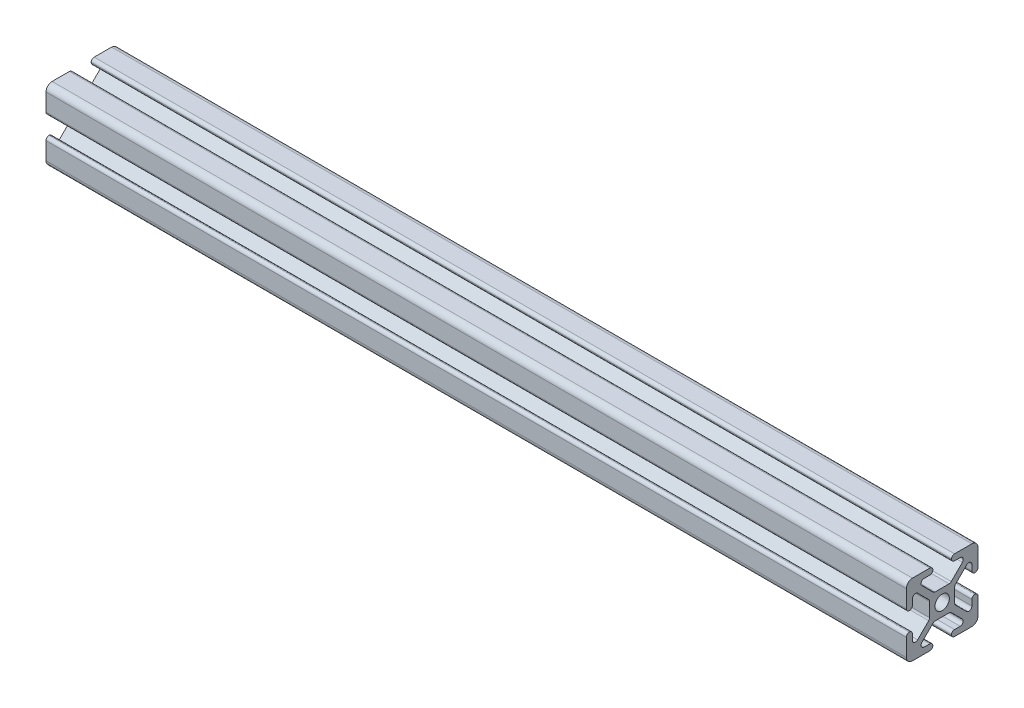
SolidWorks part; units mm, degrees
ref_plane "Front Plane" through (0, 0, 0) normal (1, 0, 0) x (0, 1, 0)
ref_plane "Top Plane" through (0, 0, 0) normal (0, 0, 1) x (0, 1, 0)
ref_plane "Right Plane" through (0, 0, 0) normal (0, 1, 0) x (-1, 0, 0)
sketch "Sketch1" plane through (0, 0, 0) normal (1, 0, 0) x (0, 1, 0)
  line L0 (0, 0) -> (0, 12.5) construction
  line L1 (-12.5, -12.5) -> (12.5, -12.5)
  line L2 (-12.5, -12.5) -> (-12.5, 12.5)
  line L3 (-12.5, 12.5) -> (12.5, 12.5)
  line L4 (12.5, -12.5) -> (12.5, 12.5)
  line L5 (-12.5, -12.5) -> (12.5, 12.5) construction
  line L6 (-12.5, 12.5) -> (12.5, -12.5) construction
  line L7 (-3.25, 12.5) -> (-3.25, 10.37)
  line L8 (-3.25, 10.37) -> (-8.8639, 10.37)
  line L9 (-8.8639, 10.37) -> (-2.8739, 4.38)
  line L10 (-2.8739, 4.38) -> (2.8739, 4.38)
  line L11 (8.8639, 10.37) -> (2.8739, 4.38)
  line L12 (3.25, 10.37) -> (8.8639, 10.37)
  line L13 (3.25, 12.5) -> (3.25, 10.37)
  line L14 (12.5, -3.25) -> (10.37, -3.25)
  line L15 (10.37, -3.25) -> (10.37, -8.8639)
  line L16 (10.37, -8.8639) -> (4.38, -2.8739)
  line L17 (4.38, 2.8739) -> (4.38, -2.8739)
  line L18 (10.37, 8.8639) -> (4.38, 2.8739)
  line L19 (10.37, 3.25) -> (10.37, 8.8639)
  line L20 (12.5, 3.25) -> (10.37, 3.25)
  line L21 (-3.25, -12.5) -> (-3.25, -10.37)
  line L22 (-3.25, -10.37) -> (-8.8639, -10.37)
  line L23 (-8.8639, -10.37) -> (-2.8739, -4.38)
  line L24 (2.8739, -4.38) -> (-2.8739, -4.38)
  line L25 (8.8639, -10.37) -> (2.8739, -4.38)
  line L26 (3.25, -10.37) -> (8.8639, -10.37)
  line L27 (3.25, -12.5) -> (3.25, -10.37)
  line L28 (-12.5, 3.25) -> (-10.37, 3.25)
  line L29 (-10.37, 3.25) -> (-10.37, 8.8639)
  line L30 (-10.37, 8.8639) -> (-4.38, 2.8739)
  line L31 (-4.38, -2.8739) -> (-4.38, 2.8739)
  line L32 (-10.37, -8.8639) -> (-4.38, -2.8739)
  line L33 (-10.37, -3.25) -> (-10.37, -8.8639)
  line L34 (-12.5, -3.25) -> (-10.37, -3.25)
  circle A0 centre (0, 0) radius 2.5
  point P0 (0, 0)
  point P15 (0, 4.38)
  dimension "D3" = 5
  dimension "D1" = 25
  dimension "D2" = 25
  dimension "D4" = 2.13
  dimension "D5" = 2.13
  dimension "D6" = 6.5
  dimension "D7" = 4.38
  dimension "D8" = 4
extrude "Boss-Extrude1" add sketch "Sketch1" along normal blind 300 contours L34 L2 L1 L21 L22 L23 L24 L25 L26 L27 L4 L14 L15 L16 L17 L18 L19 L20 L3 L13 L12 L11 L10 L9 L8 L7 L28 L29 L30 L31 L32 L33 A0 region at (0, -12.1464, -7.875)
fillet "Fillet1" radius 1.065 32 edges at (150, -10.37, -8.8639) (150, 2.8739, -4.38) (150, -2.8739, -4.38) (150, -4.38, 2.8739) (150, -4.38, -2.8739) (150, -2.8739, 4.38) (150, 2.8739, 4.38) (150, 4.38, 2.8739) (150, 4.38, -2.8739) (150, -8.8639, -10.37) (150, 8.8639, -10.37) (150, 10.37, -8.8639) (150, -10.37, 8.8639) (150, -8.8639, 10.37) (150, 10.37, 8.8639) (150, 8.8639, 10.37) (150, 12.5, 3.25) (150, -3.25, -12.5) (150, -10.37, 3.25) (150, 10.37, 3.25) (150, -10.37, -3.25) (150, -12.5, -3.25) (150, -12.5, 3.25) (150, 3.25, -10.37) (150, -3.25, -10.37) (150, 3.25, -12.5) (150, 10.37, -3.25) (150, 12.5, -3.25) (150, 3.25, 12.5) (150, 3.25, 10.37) (150, -3.25, 10.37) (150, -3.25, 12.5)
fillet "Fillet2" radius 2.13 4 edges at (150, 12.5, -12.5) (150, -12.5, -12.5) (150, 12.5, 12.5) (150, -12.5, 12.5)
sketch "Sketch2" plane through (300, 0, 0) normal (1, 0, 0) x (0, 1, 0)
  line L0 (10.37, -12.5) -> (4.315, -12.5)
  line L1 (10.37, -12.5) -> (4.315, -12.5)
  line L2 (4.315, -10.37) -> (6.2927, -10.37)
  line L3 (4.315, -10.37) -> (6.2927, -10.37)
  line L4 (7.0458, -8.5519) -> (3.1858, -4.6919)
  line L5 (7.0458, -8.5519) -> (3.1858, -4.6919)
  line L6 (2.4327, -4.38) -> (-2.4327, -4.38)
  line L7 (2.4327, -4.38) -> (-2.4327, -4.38)
  line L8 (-3.1858, -4.6919) -> (-7.0458, -8.5519)
  line L9 (-3.1858, -4.6919) -> (-7.0458, -8.5519)
  line L10 (-6.2927, -10.37) -> (-4.315, -10.37)
  line L11 (-6.2927, -10.37) -> (-4.315, -10.37)
  line L12 (-4.315, -12.5) -> (-10.37, -12.5)
  line L13 (-4.315, -12.5) -> (-10.37, -12.5)
  line L14 (-12.5, -10.37) -> (-12.5, -4.315)
  line L15 (-12.5, -10.37) -> (-12.5, -4.315)
  line L16 (-10.37, -4.315) -> (-10.37, -6.2927)
  line L17 (-10.37, -4.315) -> (-10.37, -6.2927)
  line L18 (-8.5519, -7.0458) -> (-4.6919, -3.1858)
  line L19 (-8.5519, -7.0458) -> (-4.6919, -3.1858)
  line L20 (-4.38, -2.4327) -> (-4.38, 2.4327)
  line L21 (-4.38, -2.4327) -> (-4.38, 2.4327)
  line L22 (-4.6919, 3.1858) -> (-8.5519, 7.0458)
  line L23 (-4.6919, 3.1858) -> (-8.5519, 7.0458)
  line L24 (-10.37, 6.2927) -> (-10.37, 4.315)
  line L25 (-10.37, 6.2927) -> (-10.37, 4.315)
  line L26 (-12.5, 4.315) -> (-12.5, 10.37)
  line L27 (-12.5, 4.315) -> (-12.5, 10.37)
  line L28 (-10.37, 12.5) -> (-4.315, 12.5)
  line L29 (-10.37, 12.5) -> (-4.315, 12.5)
  line L30 (-4.315, 10.37) -> (-6.2927, 10.37)
  line L31 (-4.315, 10.37) -> (-6.2927, 10.37)
  line L32 (-7.0458, 8.5519) -> (-3.1858, 4.6919)
  line L33 (-7.0458, 8.5519) -> (-3.1858, 4.6919)
  line L34 (-2.4327, 4.38) -> (2.4327, 4.38)
  line L35 (-2.4327, 4.38) -> (2.4327, 4.38)
  line L36 (3.1858, 4.6919) -> (7.0458, 8.5519)
  line L37 (3.1858, 4.6919) -> (7.0458, 8.5519)
  line L38 (6.2927, 10.37) -> (4.315, 10.37)
  line L39 (6.2927, 10.37) -> (4.315, 10.37)
  line L40 (4.315, 12.5) -> (10.37, 12.5)
  line L41 (4.315, 12.5) -> (10.37, 12.5)
  line L42 (12.5, 10.37) -> (12.5, 4.315)
  line L43 (12.5, 10.37) -> (12.5, 4.315)
  line L44 (10.37, 4.315) -> (10.37, 6.2927)
  line L45 (10.37, 4.315) -> (10.37, 6.2927)
  line L46 (8.5519, 7.0458) -> (4.6919, 3.1858)
  line L47 (8.5519, 7.0458) -> (4.6919, 3.1858)
  line L48 (4.38, 2.4327) -> (4.38, -2.4327)
  line L49 (4.38, 2.4327) -> (4.38, -2.4327)
  line L50 (4.6919, -3.1858) -> (8.5519, -7.0458)
  line L51 (4.6919, -3.1858) -> (8.5519, -7.0458)
  line L52 (10.37, -6.2927) -> (10.37, -4.315)
  line L53 (10.37, -6.2927) -> (10.37, -4.315)
  line L54 (12.5, -4.315) -> (12.5, -10.37)
  line L55 (12.5, -4.315) -> (12.5, -10.37)
  arc A0 (10.37, -12.5) -> (12.5, -10.37) centre (10.37, -10.37) ccw
  circle A1 centre (0, 0) radius 2.5
  circle A2 centre (0, 0) radius 2.5
  arc A3 (10.37, -12.5) -> (12.5, -10.37) centre (10.37, -10.37) ccw
  arc A4 (3.25, -11.435) -> (4.315, -12.5) centre (4.315, -11.435) ccw
  arc A5 (3.25, -11.435) -> (4.315, -12.5) centre (4.315, -11.435) ccw
  arc A6 (4.315, -10.37) -> (3.25, -11.435) centre (4.315, -11.435) ccw
  arc A7 (4.315, -10.37) -> (3.25, -11.435) centre (4.315, -11.435) ccw
  arc A8 (6.2927, -10.37) -> (7.0458, -8.5519) centre (6.2927, -9.305) ccw
  arc A9 (6.2927, -10.37) -> (7.0458, -8.5519) centre (6.2927, -9.305) ccw
  arc A10 (3.1858, -4.6919) -> (2.4327, -4.38) centre (2.4327, -5.445) ccw
  arc A11 (3.1858, -4.6919) -> (2.4327, -4.38) centre (2.4327, -5.445) ccw
  arc A12 (-2.4327, -4.38) -> (-3.1858, -4.6919) centre (-2.4327, -5.445) ccw
  arc A13 (-2.4327, -4.38) -> (-3.1858, -4.6919) centre (-2.4327, -5.445) ccw
  arc A14 (-7.0458, -8.5519) -> (-6.2927, -10.37) centre (-6.2927, -9.305) ccw
  arc A15 (-7.0458, -8.5519) -> (-6.2927, -10.37) centre (-6.2927, -9.305) ccw
  arc A16 (-3.25, -11.435) -> (-4.315, -10.37) centre (-4.315, -11.435) ccw
  arc A17 (-3.25, -11.435) -> (-4.315, -10.37) centre (-4.315, -11.435) ccw
  arc A18 (-4.315, -12.5) -> (-3.25, -11.435) centre (-4.315, -11.435) ccw
  arc A19 (-4.315, -12.5) -> (-3.25, -11.435) centre (-4.315, -11.435) ccw
  arc A20 (-12.5, -10.37) -> (-10.37, -12.5) centre (-10.37, -10.37) ccw
  arc A21 (-12.5, -10.37) -> (-10.37, -12.5) centre (-10.37, -10.37) ccw
  arc A22 (-11.435, -3.25) -> (-12.5, -4.315) centre (-11.435, -4.315) ccw
  arc A23 (-11.435, -3.25) -> (-12.5, -4.315) centre (-11.435, -4.315) ccw
  arc A24 (-10.37, -4.315) -> (-11.435, -3.25) centre (-11.435, -4.315) ccw
  arc A25 (-10.37, -4.315) -> (-11.435, -3.25) centre (-11.435, -4.315) ccw
  arc A26 (-10.37, -6.2927) -> (-8.5519, -7.0458) centre (-9.305, -6.2927) ccw
  arc A27 (-10.37, -6.2927) -> (-8.5519, -7.0458) centre (-9.305, -6.2927) ccw
  arc A28 (-4.6919, -3.1858) -> (-4.38, -2.4327) centre (-5.445, -2.4327) ccw
  arc A29 (-4.6919, -3.1858) -> (-4.38, -2.4327) centre (-5.445, -2.4327) ccw
  arc A30 (-4.38, 2.4327) -> (-4.6919, 3.1858) centre (-5.445, 2.4327) ccw
  arc A31 (-4.38, 2.4327) -> (-4.6919, 3.1858) centre (-5.445, 2.4327) ccw
  arc A32 (-8.5519, 7.0458) -> (-10.37, 6.2927) centre (-9.305, 6.2927) ccw
  arc A33 (-8.5519, 7.0458) -> (-10.37, 6.2927) centre (-9.305, 6.2927) ccw
  arc A34 (-11.435, 3.25) -> (-10.37, 4.315) centre (-11.435, 4.315) ccw
  arc A35 (-11.435, 3.25) -> (-10.37, 4.315) centre (-11.435, 4.315) ccw
  arc A36 (-12.5, 4.315) -> (-11.435, 3.25) centre (-11.435, 4.315) ccw
  arc A37 (-12.5, 4.315) -> (-11.435, 3.25) centre (-11.435, 4.315) ccw
  arc A38 (-10.37, 12.5) -> (-12.5, 10.37) centre (-10.37, 10.37) ccw
  arc A39 (-10.37, 12.5) -> (-12.5, 10.37) centre (-10.37, 10.37) ccw
  arc A40 (-3.25, 11.435) -> (-4.315, 12.5) centre (-4.315, 11.435) ccw
  arc A41 (-3.25, 11.435) -> (-4.315, 12.5) centre (-4.315, 11.435) ccw
  arc A42 (-4.315, 10.37) -> (-3.25, 11.435) centre (-4.315, 11.435) ccw
  arc A43 (-4.315, 10.37) -> (-3.25, 11.435) centre (-4.315, 11.435) ccw
  arc A44 (-6.2927, 10.37) -> (-7.0458, 8.5519) centre (-6.2927, 9.305) ccw
  arc A45 (-6.2927, 10.37) -> (-7.0458, 8.5519) centre (-6.2927, 9.305) ccw
  arc A46 (-3.1858, 4.6919) -> (-2.4327, 4.38) centre (-2.4327, 5.445) ccw
  arc A47 (-3.1858, 4.6919) -> (-2.4327, 4.38) centre (-2.4327, 5.445) ccw
  arc A48 (2.4327, 4.38) -> (3.1858, 4.6919) centre (2.4327, 5.445) ccw
  arc A49 (2.4327, 4.38) -> (3.1858, 4.6919) centre (2.4327, 5.445) ccw
  arc A50 (7.0458, 8.5519) -> (6.2927, 10.37) centre (6.2927, 9.305) ccw
  arc A51 (7.0458, 8.5519) -> (6.2927, 10.37) centre (6.2927, 9.305) ccw
  arc A52 (3.25, 11.435) -> (4.315, 10.37) centre (4.315, 11.435) ccw
  arc A53 (3.25, 11.435) -> (4.315, 10.37) centre (4.315, 11.435) ccw
  arc A54 (4.315, 12.5) -> (3.25, 11.435) centre (4.315, 11.435) ccw
  arc A55 (4.315, 12.5) -> (3.25, 11.435) centre (4.315, 11.435) ccw
  arc A56 (12.5, 10.37) -> (10.37, 12.5) centre (10.37, 10.37) ccw
  arc A57 (12.5, 10.37) -> (10.37, 12.5) centre (10.37, 10.37) ccw
  arc A58 (11.435, 3.25) -> (12.5, 4.315) centre (11.435, 4.315) ccw
  arc A59 (11.435, 3.25) -> (12.5, 4.315) centre (11.435, 4.315) ccw
  arc A60 (10.37, 4.315) -> (11.435, 3.25) centre (11.435, 4.315) ccw
  arc A61 (10.37, 4.315) -> (11.435, 3.25) centre (11.435, 4.315) ccw
  arc A62 (10.37, 6.2927) -> (8.5519, 7.0458) centre (9.305, 6.2927) ccw
  arc A63 (10.37, 6.2927) -> (8.5519, 7.0458) centre (9.305, 6.2927) ccw
  arc A64 (4.6919, 3.1858) -> (4.38, 2.4327) centre (5.445, 2.4327) ccw
  arc A65 (4.6919, 3.1858) -> (4.38, 2.4327) centre (5.445, 2.4327) ccw
  arc A66 (4.38, -2.4327) -> (4.6919, -3.1858) centre (5.445, -2.4327) ccw
  arc A67 (4.38, -2.4327) -> (4.6919, -3.1858) centre (5.445, -2.4327) ccw
  arc A68 (8.5519, -7.0458) -> (10.37, -6.2927) centre (9.305, -6.2927) ccw
  arc A69 (8.5519, -7.0458) -> (10.37, -6.2927) centre (9.305, -6.2927) ccw
  arc A70 (11.435, -3.25) -> (10.37, -4.315) centre (11.435, -4.315) ccw
  arc A71 (11.435, -3.25) -> (10.37, -4.315) centre (11.435, -4.315) ccw
  arc A72 (12.5, -4.315) -> (11.435, -3.25) centre (11.435, -4.315) ccw
  arc A73 (12.5, -4.315) -> (11.435, -3.25) centre (11.435, -4.315) ccw
  dimension "D1" = 0
